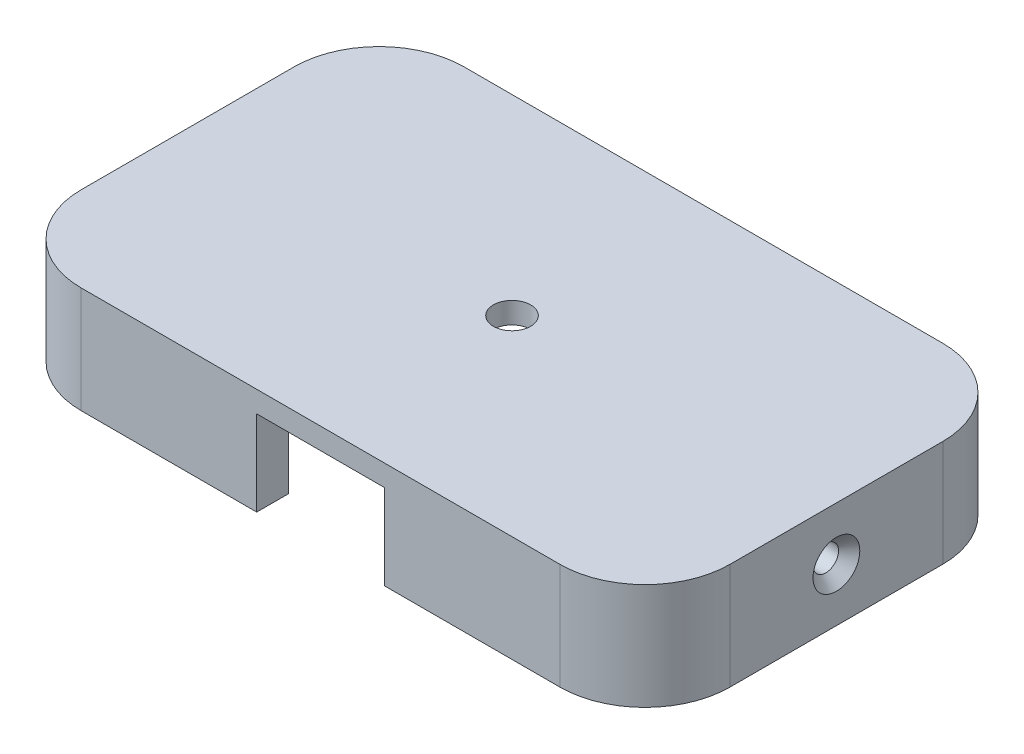
SolidWorks part; units mm, degrees
ref_plane "Front Plane" through (0, 0, 0) normal (0, 0, 1) x (1, 0, 0)
ref_plane "Top Plane" through (0, 0, 0) normal (0, 1, 0) x (1, 0, 0)
ref_plane "Right Plane" through (0, 0, 0) normal (1, 0, 0) x (0, 0, -1)
sketch "Sketch1" plane through (0, 0, 0) normal (0, 1, 0) x (1, 0, 0)
  line L0 (-22.5, 18) -> (22.5, 18)
  line L1 (-22.5, -15) -> (22.5, -15)
  line L2 (-27.5, -10) -> (-27.5, 10)
  line L3 (-22.5, 15) -> (22.5, 15)
  line L4 (27.5, -10) -> (27.5, 10)
  line L5 (-27.5, -15) -> (27.5, 15) construction
  line L6 (-27.5, 15) -> (27.5, -15) construction
  line L7 (30.5, -10) -> (30.5, 10)
  line L8 (-22.5, -18) -> (22.5, -18)
  line L9 (-30.5, -10) -> (-30.5, 10)
  arc A0 (22.5, 15) -> (27.5, 10) centre (22.5, 10) cw
  arc A1 (27.5, -10) -> (22.5, -15) centre (22.5, -10) cw
  arc A2 (-22.5, -15) -> (-27.5, -10) centre (-22.5, -10) cw
  arc A3 (-27.5, 10) -> (-22.5, 15) centre (-22.5, 10) cw
  arc A4 (22.5, 18) -> (30.5, 10) centre (22.5, 10) cw
  arc A5 (30.5, -10) -> (22.5, -18) centre (22.5, -10) cw
  arc A6 (-22.5, -18) -> (-30.5, -10) centre (-22.5, -10) cw
  arc A7 (-30.5, 10) -> (-22.5, 18) centre (-22.5, 10) cw
  point P0 (0, 0)
  dimension "D3" = 5
  dimension "D1" = 55
  dimension "D2" = 30
  dimension "D4" = 3
extrude "Boss-Extrude1" add sketch "Sketch1" against normal blind 10
extrude "Boss-Extrude2" add sketch "Sketch1<2>" against normal blind 2 contours A3 L2 A2 L1 A1 L4 A0 L3 region at (0, 0, 0)
sketch "Sketch1<2>" plane through (0, 0, 0) normal (0, 1, 0) x (1, 0, 0) same geometry as "Sketch1"
hole_wizard "CSK for M2 Flat Head Machine Screw1" positions "Sketch2" profile "Sketch4" countersink size "M2" standard "ANSI Metric"
sketch "Sketch2" plane through (30.5, 0, 0) normal (1, 0, 0) x (0, 0, -1)
  line L0 (-10, 0) -> (10, -10) construction
  point P6 (0, -5)
sketch "Sketch4" plane through (30.5, -5, 0) normal (0, 1, 0) x (0, 0, -1)
  line L0 (0, 0) -> (0, 10.721)
  line L1 (0, 10.721) -> (1.2, 10)
  line L2 (1.2, 10) -> (1.2, 1)
  line L3 (1.2, 1) -> (2.2, 0)
  line L5 (2.2, 0) -> (0, 0)
  line L6 (-1.2, 1) -> (-2.2, 0) construction
  line L10 (0, 10.721) -> (-1.2, 10) construction
  line L11 (0, -6.35) -> (0, 107.95) construction
  dimension "Hole Dia." = 2.4
  dimension "Hole Depth" = 10
  dimension "Near C'Sink Dia." = 4.4
  dimension "Near C'Sink Angle" = 90
  dimension "Drill Angle" = 118
mirror "Mirror1" about plane through (0, 0, 0) normal (1, 0, 0) of "CSK for M2 Flat Head Machine Screw1"
hole_wizard "Ø3.5 (3.5) Diameter Hole1" positions "Sketch6" profile "Sketch7" hole size "Ø3.5" standard "ANSI Metric" end condition through all
sketch "Sketch6" plane through (0, -2, 0) normal (0, -1, 0) x (-1, 0, 0)
  point P0 (0, 0)
sketch "Sketch7" plane through (0, -2, 0) normal (1, 0, 0) x (0, 0, -1)
  line L0 (0, 0) -> (0, 2)
  line L1 (0, 2) -> (1.75, 2)
  line L2 (1.75, 2) -> (1.75, 0)
  line L5 (1.75, 0) -> (0, 0)
  line L11 (0, -6.35) -> (0, 107.95) construction
  dimension "Thru Hole Dia." = 3.5
  dimension "Thru Hole Depth" = 2
sketch "Sketch8" plane through (0, 0, 18) normal (0, 0, 1) x (1, 0, 0)
  line L0 (-22.5, -10) -> (22.5, -10) construction
  line L1 (6, -2) -> (-6, -2)
  line L2 (6, -2) -> (6, -10)
  line L3 (6, -10) -> (-6, -10)
  line L4 (-6, -2) -> (-6, -10)
  line L5 (6, -2) -> (-6, -10) construction
  line L6 (6, -10) -> (-6, -2) construction
  line L7 (0, 0) -> (0, -6) construction
  line L8 (-22.5, 0) -> (22.5, 0) construction
  point P0 (0, -6)
  dimension "D1" = 12
  dimension "D2" = 8
extrude "Cut-Extrude1" cut sketch "Sketch8" against normal blind 5
